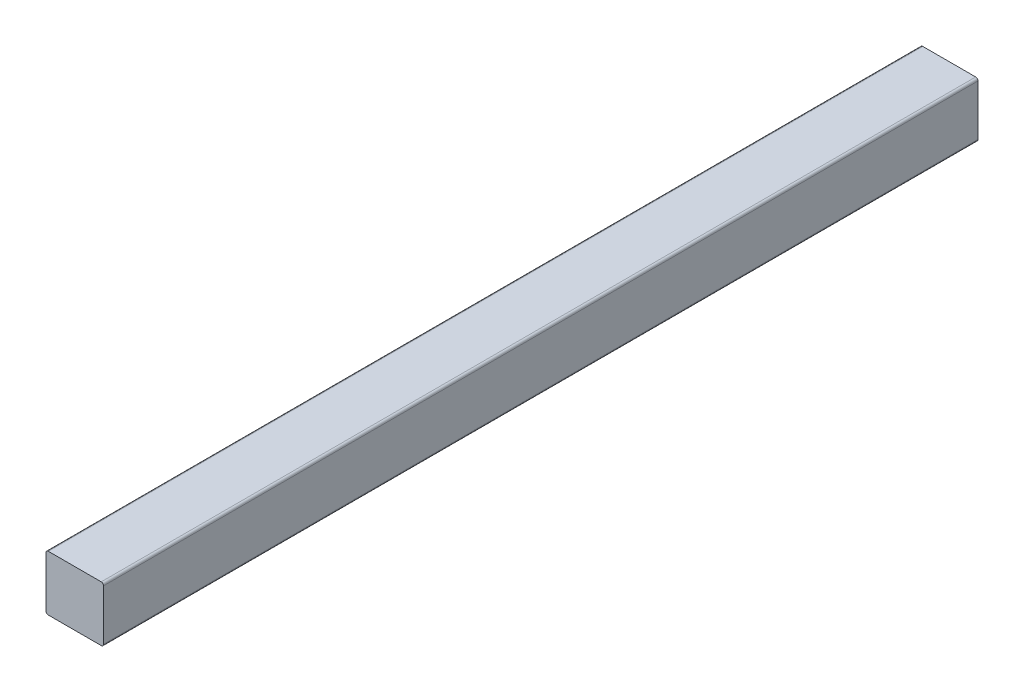
SolidWorks part; units mm, degrees
material "Plain Carbon Steel"
ref_plane "Front Plane" through (0, 0, 0) normal (0, 0, 1) x (1, 0, 0)
ref_plane "Top Plane" through (0, 0, 0) normal (0, 1, 0) x (1, 0, 0)
ref_plane "Right Plane" through (0, 0, 0) normal (1, 0, 0) x (0, 0, -1)
sketch "Sketch1" plane through (0, 0, 0) normal (0, 0, 1) x (1, 0, 0)
  line L0 (50, 2) -> (50, 0) construction
  line L1 (2, 0) -> (48, 0)
  line L2 (0, 2) -> (0, 46)
  line L3 (2, 48) -> (48, 48)
  line L4 (50, 2) -> (50, 46)
  line L5 (50, 0) -> (48, 0) construction
  line L6 (0, 2) -> (0, 0) construction
  line L7 (0, 0) -> (2, 0) construction
  line L9 (-250, 0) -> (50, 0) construction
  arc A0 (2, 0) -> (0, 2) centre (2, 2) cw
  arc A1 (48, 0) -> (50, 2) centre (48, 2) ccw
  arc A2 (48, 48) -> (50, 46) centre (48, 46) cw
  arc A3 (0, 46) -> (2, 48) centre (2, 46) cw
  point P7 (50, 0)
  point P12 (50, 48)
  point P15 (0, 48)
  point P16 (0, 0)
  dimension "D3" = 2
  dimension "D1" = 48
  dimension "D2" = 50
extrude "Boss-Extrude1" add sketch "Sketch1" along normal blind 760
sketch "Center_lines" plane through (0, 48, 0) normal (0, 1, 0) x (1, 0, 0)
  line L0 (25, -181.2374) -> (25, -578.7626) construction
  line L1 (0, -380) -> (50, -380) construction
  line L2 (48, 0) -> (2, 0) construction
  line L3 (48, -760) -> (48, 0) construction
  line L4 (0, -760) -> (0, 0) construction
  point P6 (25, 0)
  point P7 (25, -380)
  point P10 (48, -380)
  point P15 (25, -380)
sketch "Tube_end_reference" plane through (0, 0, 760) normal (0, 0, 1) x (1, 0, 0)
  line L0 (50, 2) -> (50, 46) construction
  line L1 (50, 48) -> (0, 48) construction
  line L2 (50, 48) -> (50, 0) construction
  line L3 (50, 0) -> (0, 0) construction
  line L4 (0, 48) -> (0, 0) construction
  line L5 (0, 46) -> (0, 2) construction
  line L6 (0, 48) -> (50, 48) construction
  line L7 (2, 0) -> (48, 0) construction
sketch "Tube_corners_R" plane through (50, 0, 0) normal (1, 0, 0) x (0, 0, -1)
  line L0 (-760, 0) -> (0, 0) construction
  line L1 (-760, 48) -> (0, 48) construction
sketch "Tube_corners_L" plane through (0, 0, 0) normal (-1, 0, 0) x (0, 0, 1)
  line L0 (760, 48) -> (0, 48) construction
  line L1 (760, 0) -> (0, 0) construction
equation "\"Movement\"= 460"
equation "\"Block spacing\" = 300"
equation "\"Base length\"= \"Movement\" + \"Block spacing\""
equation "\"D1@Boss-Extrude1\"= \"Base length\""
